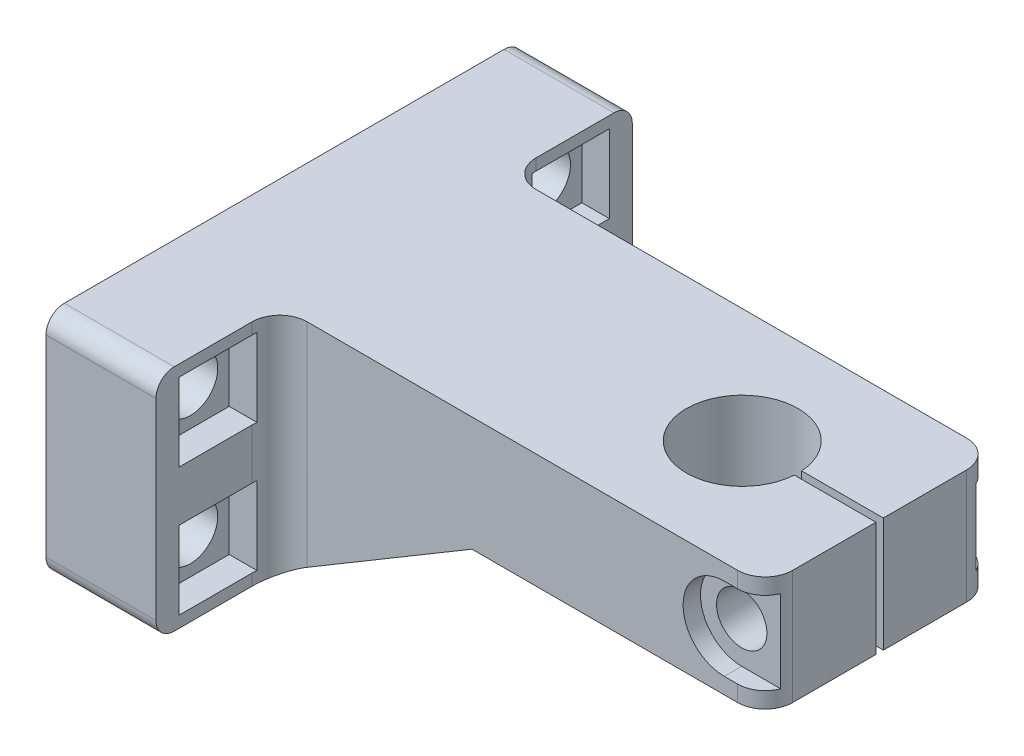
SolidWorks part; units mm, degrees
note: The reader was unsure of these and kept them because the rebuilt part matched: shared geometry of "Sketch7<3>".
ref_plane "Front Plane" through (0, 0, 0) normal (0, 0, 1) x (1, 0, 0)
ref_plane "Top Plane" through (0, 0, 0) normal (0, 1, 0) x (1, 0, 0)
ref_plane "Right Plane" through (0, 0, 0) normal (1, 0, 0) x (0, 0, -1)
sketch "Sketch1" plane through (0, 0, 0) normal (0, 0, 1) x (1, 0, 0)
  line L0 (12, -25) -> (33, -12.5)
  line L1 (0, 0) -> (65, 0)
  line L2 (0, 0) -> (0, -25)
  line L3 (0, -25) -> (12, -25)
  line L4 (65, 0) -> (65, -12.5)
  line L5 (33, -12.5) -> (65, -12.5)
  dimension "D1" = 12.5
  dimension "D2" = 65
  dimension "D3" = 12
  dimension "D4" = 32
  dimension "D5" = 25
extrude "Boss-Extrude1" add sketch "Sketch1" along normal mid plane 25
sketch "Sketch2" plane through (0, 0, 0) normal (-1, 0, 0) x (0, 0, 1)
  line L0 (12.5, -25) -> (-12.5, -25) construction
  line L1 (-26, 0) -> (26, 0)
  line L2 (-26, 0) -> (-26, -25)
  line L3 (-26, -25) -> (26, -25)
  line L4 (26, 0) -> (26, -25)
  line L6 (-19.25, 0) -> (-19.25, -25) construction
  line L7 (-19.25, -12.5) -> (-26, -12.5) construction
  line L8 (-19.25, -12.5) -> (-12.5, -12.5) construction
  line L9 (-12.5, 0) -> (-12.5, -25) construction
  line L10 (0, 0) -> (0, -25) construction
  circle A0 centre (-19.25, -5.5) radius 3
  circle A1 centre (-19.25, -19.5) radius 3
  circle A2 centre (19.25, -19.5) radius 3
  circle A3 centre (19.25, -5.5) radius 3
  dimension "D2" = 14
  dimension "D3" = 6
  dimension "D1" = 38.5
extrude "Boss-Extrude2" add sketch "Sketch2" against normal blind 12
sketch "Sketch4" plane through (0, 0, 0) normal (0, 1, 0) x (1, 0, 0)
  line L0 (65, -12.5) -> (65, 12.5) construction
  line L1 (50, 0) -> (65, 0) construction
  line L2 (56.0869, -0.4) -> (65, -0.4)
  line L3 (56.0869, 0.4) -> (65, 0.4)
  line L4 (50, 0.4) -> (65, 0.4) construction
  line L5 (50, 0) -> (65, 0) construction
  line L6 (50, -0.4) -> (65, -0.4) construction
  line L7 (65, 0.4) -> (65, -0.4)
  arc A0 (56.0869, 0.4) -> (56.0869, -0.4) centre (50, 0) ccw
  dimension "D2" = 12.2
  dimension "D1" = 15
  dimension "D3" = 0.4
  dimension "D4" = 0.4
extrude "Cut-Extrude2" cut sketch "Sketch4" against normal through all
sketch "Sketch5" plane through (0, 0, 0) normal (-1, 0, 0) x (0, 0, 1)
  line L4 (-26, 0) -> (-26, -25)
  line L5 (-26, -25) -> (26, -25)
  line L6 (26, -25) -> (26, 0)
  line L7 (26, 0) -> (-26, 0)
  line L8 (-26, 0) -> (-26, -25)
  line L9 (-26, -25) -> (26, -25)
  line L10 (26, -25) -> (26, 0)
  line L11 (26, 0) -> (-26, 0)
  circle A0 centre (19.25, -19.5) radius 3 construction
  circle A1 centre (19.25, -5.5) radius 3 construction
  circle A2 centre (-19.25, -5.5) radius 3 construction
  circle A3 centre (-19.25, -19.5) radius 3 construction
  circle A12 centre (19.25, -19.5) radius 3
  circle A13 centre (19.25, -5.5) radius 3
  circle A14 centre (-19.25, -5.5) radius 3
  circle A15 centre (-19.25, -19.5) radius 3
  dimension "D1" = 0
extrude "Boss-Extrude3" [suppressed] add sketch "Sketch5" along normal blind 2
fillet "Fillet1" radius 2 4 edges at (6, -25, -26) (6, 0, -26) (6, -25, 26) (6, 0, 26)
fillet "Fillet2" radius 3 2 edges at (65, -6.25, -12.5) (65, -6.25, 12.5)
sketch "Sketch7" plane through (0, 0, -0.4) normal (0, 0, 1) x (1, 0, 0)
  line L0 (56.0869, -6.25) -> (65, -6.25) construction
  line L1 (60.5434, -1.75) -> (65, -1.75)
  line L2 (65, -1.75) -> (65, -10.75)
  line L3 (65, -10.75) -> (60.5434, -10.75)
  line L4 (65, -12.5) -> (65, 0)
  line L5 (65, 0) -> (56.0869, 0)
  line L6 (56.0869, 0) -> (56.0869, -12.5)
  line L7 (56.0869, -12.5) -> (65, -12.5)
  line L8 (65, -12.5) -> (65, 0) construction
  line L9 (65, 0) -> (56.0869, 0) construction
  line L10 (56.0869, 0) -> (56.0869, -12.5) construction
  line L11 (56.0869, -12.5) -> (65, -12.5) construction
  circle A0 centre (60.5434, -6.25) radius 2.75
  arc A1 (60.5434, -1.75) -> (60.5434, -10.75) centre (60.5434, -6.25) ccw
  dimension "D2" = 5.5
  dimension "D3" = 9
  dimension "D1" = 0
extrude "Cut-Extrude3" cut sketch "Sketch7" against normal through all both and the other way through all contours A0
extrude "Cut-Extrude4" cut sketch "Sketch7<3>" along normal blind 20 from offset 11
sketch "Sketch7<3>" plane through (0, 0, -0.4) normal (0, 0, 1) x (1, 0, 0) same geometry as "Sketch7"
sketch "Sketch9" plane through (0, 0, -12.5) normal (0, 0, -1) x (-1, 0, 0)
  line L1 (-64.6684, -10.375) -> (-56.4184, -10.375)
  line L2 (-64.6684, -10.375) -> (-64.6684, -2.125)
  line L3 (-64.6684, -2.125) -> (-56.4184, -2.125)
  line L4 (-56.4184, -10.375) -> (-56.4184, -2.125)
  line L5 (-64.6684, -10.375) -> (-56.4184, -2.125) construction
  line L6 (-64.6684, -2.125) -> (-56.4184, -10.375) construction
  point P0 (-60.5434, -6.25)
  dimension "D1" = 8.25
extrude "Cut-Extrude5" cut sketch "Sketch9" against normal blind 3
sketch "Sketch12" plane through (12, 0, 0) normal (1, 0, 0) x (0, 0, -1)
  line L0 (23.5, -1.25) -> (23.5, -9.75)
  line L1 (-15, -1.25) -> (-23.5, -1.25)
  line L2 (-15, -1.25) -> (-15, -9.75)
  line L3 (-15, -9.75) -> (-23.5, -9.75)
  line L4 (-23.5, -1.25) -> (-23.5, -9.75)
  line L5 (-15, -1.25) -> (-23.5, -9.75) construction
  line L6 (-15, -9.75) -> (-23.5, -1.25) construction
  line L7 (23.5, -1.25) -> (15, -1.25)
  line L8 (15, -1.25) -> (15, -9.75)
  line L9 (23.5, -9.75) -> (15, -9.75)
  line L10 (23.5, -9.75) -> (15, -1.25) construction
  line L11 (23.5, -1.25) -> (15, -9.75) construction
  line L12 (23.5, -15.25) -> (23.5, -23.75)
  line L13 (23.5, -15.25) -> (15, -15.25)
  line L14 (15, -15.25) -> (15, -23.75)
  line L15 (23.5, -23.75) -> (15, -23.75)
  line L16 (23.5, -23.75) -> (15, -15.25) construction
  line L17 (23.5, -15.25) -> (15, -23.75) construction
  line L18 (-15, -15.25) -> (-15, -23.75)
  line L19 (-15, -15.25) -> (-23.5, -15.25)
  line L20 (-23.5, -15.25) -> (-23.5, -23.75)
  line L21 (-15, -23.75) -> (-23.5, -23.75)
  line L22 (-15, -23.75) -> (-23.5, -15.25) construction
  line L23 (-15, -15.25) -> (-23.5, -23.75) construction
  point P0 (-19.25, -5.5)
  point P6 (-19.25, -19.5)
  point P8 (-19.25, -19.5)
  point P21 (19.25, -5.5)
  dimension "D1" = 8.5
  dimension "D2" = 2
  dimension "D3" = 2
extrude "Cut-Extrude7" cut sketch "Sketch12" against normal blind 3
fillet "Fillet3" radius 3 2 edges at (12, -12.5, -12.5) (12, -12.5, 12.5)
sketch "Sketch11" plane through (12, 0, 0) normal (1, 0, 0) x (0, 0, -1)
  line L0 (-25.2604, -5.5) -> (-19.25, -11.5104)
  line L1 (-25.2604, -5.5) -> (-19.25, 0.5104)
  line L2 (-19.25, -11.5104) -> (-13.2396, -5.5)
  line L3 (-19.25, 0.5104) -> (-13.2396, -5.5)
  line L4 (-25.2604, -5.5) -> (-13.2396, -5.5) construction
  line L5 (-19.25, -11.5104) -> (-19.25, 0.5104) construction
  line L6 (13.2396, -5.5) -> (19.25, -11.5104)
  line L7 (13.2396, -5.5) -> (19.25, 0.5104)
  line L8 (19.25, 0.5104) -> (25.2604, -5.5)
  line L9 (19.25, -11.5104) -> (25.2604, -5.5)
  line L10 (13.2396, -19.5) -> (19.25, -25.5104)
  line L11 (13.2396, -19.5) -> (19.25, -13.4896)
  line L12 (19.25, -13.4896) -> (25.2604, -19.5)
  line L13 (19.25, -25.5104) -> (25.2604, -19.5)
  line L14 (-25.2604, -19.5) -> (-19.25, -25.5104)
  line L15 (-25.2604, -19.5) -> (-19.25, -13.4896)
  line L16 (-19.25, -13.4896) -> (-13.2396, -19.5)
  line L17 (-19.25, -25.5104) -> (-13.2396, -19.5)
  line L18 (13.2396, -19.5) -> (25.2604, -19.5) construction
  circle A0 centre (-19.25, -5.5) radius 3 construction
  circle A1 centre (19.25, -19.5) radius 3 construction
  point P0 (19.25, -19.5)
  point P1 (-19.25, -5.5)
  dimension "D1" = 8.5
  dimension "D2" = 2
  dimension "D3" = 2
extrude "Cut-Extrude6" [suppressed] cut sketch "Sketch11" against normal blind 3
